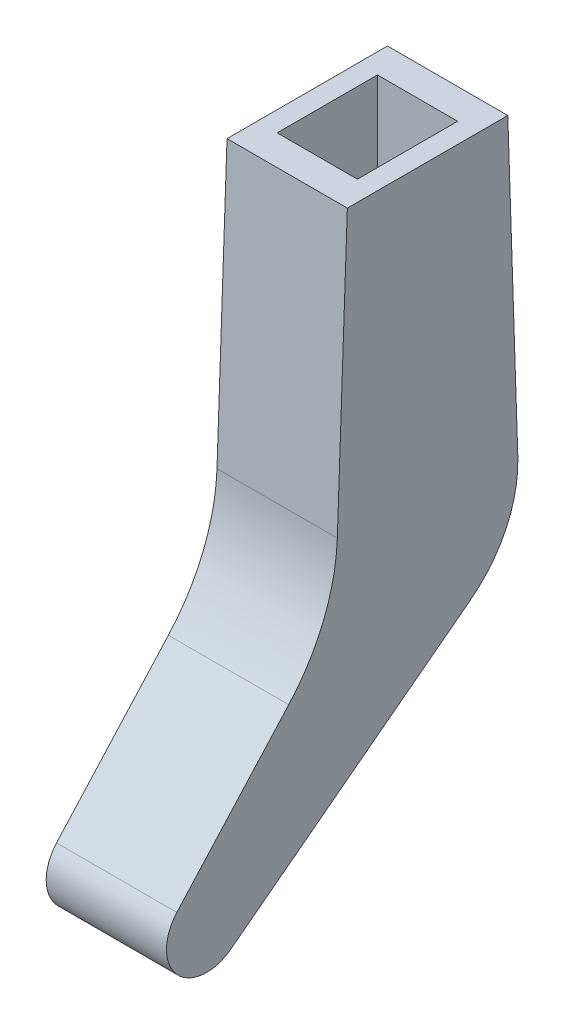
SolidWorks part; units mm, degrees
material "Rubber"
ref_plane "Front Plane" through (0, 0, 0) normal (0, 0, 1) x (1, 0, 0)
ref_plane "Top Plane" through (0, 0, 0) normal (0, 1, 0) x (1, 0, 0)
ref_plane "Right Plane" through (0, 0, 0) normal (1, 0, 0) x (0, 0, -1)
sketch "Sketch1" plane through (0, 0, 0) normal (1, 0, 0) x (0, 0, -1)
  line L0 (-5, 20) -> (-8, 20)
  line L1 (-5, 0) -> (5, 0)
  line L2 (-5, 0) -> (-5, 20)
  line L3 (-5, 20) -> (5, 20)
  line L4 (5, 0) -> (5, 20)
  line L5 (-8, 20) -> (-9, -8)
  line L6 (-13.8475, -19.9623) -> (-25.0029, -32.3197)
  line L7 (-19.6095, -38.1817) -> (4.2532, -20)
  line L8 (9, -10) -> (8, 20)
  line L9 (8, 20) -> (5, 20)
  circle A0 centre (0, 0) radius 5
  arc A1 (-9, -8) -> (-13.8475, -19.9623) centre (-27.8444, -7.327) cw
  arc A2 (-25.0029, -32.3197) -> (-19.6095, -38.1817) centre (-22.0337, -35) ccw
  arc A3 (4.2532, -20) -> (9, -10) centre (-3.0599, -10.402) ccw
  dimension "D1" = 10
  dimension "D3" = 4
  dimension "D2" = 20
  dimension "D4" = 30
  dimension "D5" = 3
  dimension "D6" = 3
  dimension "D7" = 30
  dimension "D8" = 35
  dimension "D9" = 9
  dimension "D10" = 28
  dimension "D11" = 9
  dimension "D12" = 40
  dimension "D13" = 11
extrude "Boss-Extrude1" add sketch "Sketch1" along normal mid plane 8 contours L7 A3 L8 L9 L4 A0 L2 L0 L5 A1 L6 A2 region at (0, -13.2175, 5.2441)
extrude "Boss-Extrude2" add sketch "Sketch1<3>" along normal blind 2 from surface contours A0 L4 L3 L2 | L7 A3 L8 L9 L4 A0 L2 L0 L5 A1 L6 A2 | L1 A0 | L1 A0 region at (0, -13.2175, 5.2441) region at (0, 11.9248, 0) region at (0, 2.1221, 0) region at (0, -2.1221, 0) starting at face at (4, -4.7438, 4.5507)
sketch "Sketch1<3>" plane through (0, 0, 0) normal (1, 0, 0) x (0, 0, -1) same geometry as "Sketch1"
extrude "Boss-Extrude3" add sketch "Sketch1<4>" against normal blind 2 from surface contours L1 A0 | L1 A0 | A0 L4 L3 L2 | L7 A3 L8 L9 L4 A0 L2 L0 L5 A1 L6 A2 region at (0, -13.2175, 5.2441) region at (0, 11.9248, 0) region at (0, 2.1221, 0) region at (0, -2.1221, 0) starting at face at (-4, -4.7438, 4.5507)
sketch "Sketch1<4>" plane through (0, 0, 0) normal (1, 0, 0) x (0, 0, -1) same geometry as "Sketch1"
move or copy body "Body-Move/Copy1" [suppressed] bodies to move or copy 103
